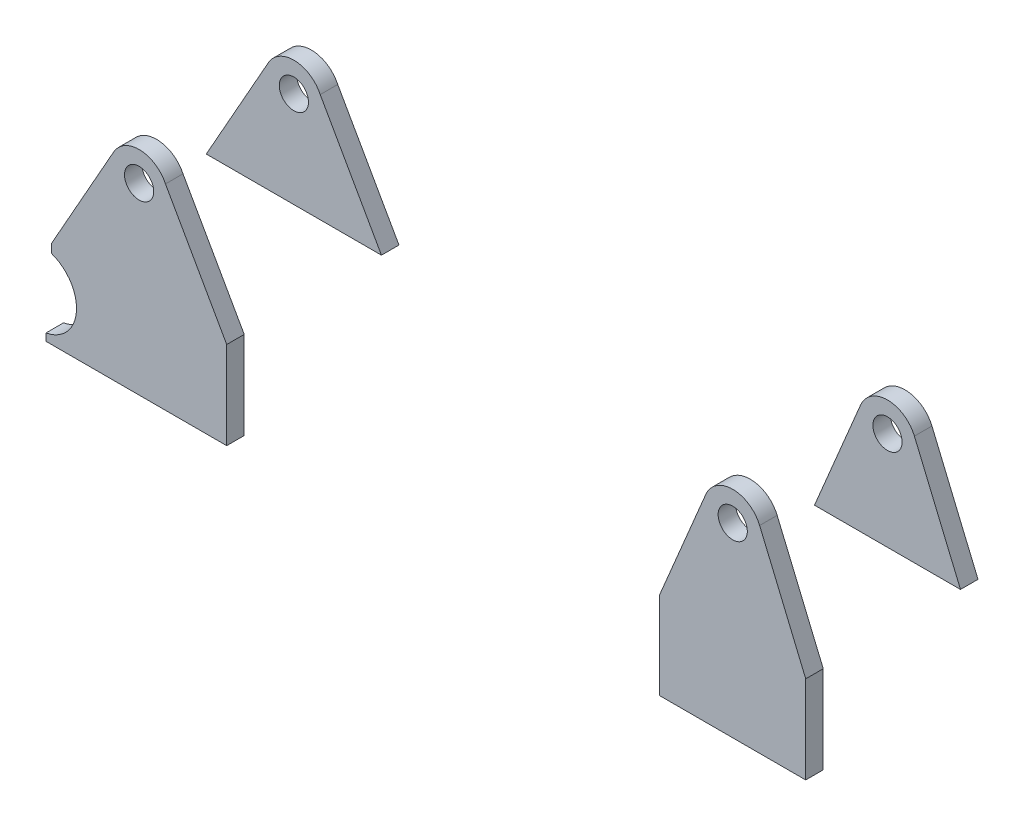
SolidWorks part; units mm, degrees
ref_plane "Front Plane" through (0, 0, 0) normal (0, 0, 1) x (1, 0, 0)
ref_plane "Top Plane" through (0, 0, 0) normal (0, 1, 0) x (1, 0, 0)
ref_plane "Right Plane" through (0, 0, 0) normal (1, 0, 0) x (0, 0, -1)
sketch "Sketch1" plane through (0, 0, 0) normal (0, 0, 1) x (1, 0, 0)
  line L0 (-745.1446, -553.3409) -> (-146.7575, -553.3409) construction
  line L1 (-745.1446, -553.3409) -> (-146.7575, -553.3409)
  line L2 (-737.4286, -553.3409) -> (-716.1399, -515.5758)
  line L3 (-698.3946, -516.1984) -> (-677.4286, -553.3409)
  line L4 (-711.9899, -518.4383) -> (-702.8674, -522.5346) construction
  line L5 (-500.2511, -516.4564) -> (-508.0021, -522.7748) construction
  line L6 (-707.4286, -520.4864) -> (-707.4286, -553.3409) construction
  line L7 (-513.3474, -515.7455) -> (-529.1266, -553.3409)
  line L9 (-494.9058, -515.7455) -> (-479.1266, -553.3409)
  line L11 (-745.1446, -583.3409) -> (-146.7582, -583.3409) construction
  line L12 (-739.3144, -583.3409) -> (-146.7582, -583.3409)
  line L16 (-677.4286, -553.3409) -> (-677.4286, -583.3409)
  line L17 (-737.4286, -553.3409) -> (-737.4286, -556.3319)
  line L19 (-504.1266, -519.6156) -> (-504.1266, -553.3409) construction
  line L20 (-529.1266, -553.3409) -> (-529.1266, -583.3409)
  line L21 (-529.1266, -583.3409) -> (-479.1266, -583.3409)
  line L22 (-479.1266, -583.3409) -> (-479.1266, -553.3409)
  line L23 (-739.3144, -580.8409) -> (-739.3144, -583.3409)
  circle A0 centre (-707.4286, -520.4864) radius 10
  circle A2 centre (-504.1266, -519.6156) radius 10
  arc A3 (-728.8602, -568.3411) -> (-754.2602, -568.3411) centre (-741.5602, -568.3411) ccw
  arc A4 (-728.8602, -568.3411) -> (-737.4286, -556.3319) centre (-741.5602, -568.3411) ccw
  arc A5 (-754.2602, -568.3411) -> (-728.8602, -568.3411) centre (-741.5602, -568.3411) ccw
  arc A6 (-739.3144, -580.8409) -> (-728.8602, -568.3411) centre (-741.5602, -568.3411) ccw
  spline S1 degree 3 poles (-702.4287, -520.5175) (-702.3667, -510.5177) (-712.3665, -510.4556) (-712.4285, -520.4554) (-712.4906, -530.4552) (-702.4908, -530.5173) (-702.4287, -520.5175) (-702.3667, -510.5177) (-712.3665, -510.4556) knots -0.5 0 0 0 0.5 0.5 0.5 1 1 1 1.5 1.5 1.5 weights 1 0.333333 0.333333 1 0.333333 0.333333 1 0.333333 0.333333 only from (-702.4287, -520.5175) to (-702.4287, -520.5175) construction
  spline S2 degree 3 poles (-499.1267, -519.6466) (-499.0647, -509.6468) (-509.0645, -509.5848) (-509.1265, -519.5846) (-509.1886, -529.5844) (-499.1887, -529.6464) (-499.1267, -519.6466) (-499.0647, -509.6468) (-509.0645, -509.5848) knots -0.5 0 0 0 0.5 0.5 0.5 1 1 1 1.5 1.5 1.5 weights 1 0.333333 0.333333 1 0.333333 0.333333 1 0.333333 0.333333 only from (-499.1267, -519.6466) to (-499.1267, -519.6466) construction
  spline S3 degree 3 poles (-702.4287, -520.5175) (-702.3667, -510.5177) (-712.3665, -510.4556) (-712.4285, -520.4554) (-712.4906, -530.4552) (-702.4908, -530.5173) (-702.4287, -520.5175) (-702.3667, -510.5177) (-712.3665, -510.4556) knots -0.5 0 0 0 0.5 0.5 0.5 1 1 1 1.5 1.5 1.5 weights 1 0.333333 0.333333 1 0.333333 0.333333 1 0.333333 0.333333 only from (-702.4287, -520.5175) to (-702.4287, -520.5175)
  spline S4 degree 3 poles (-499.1267, -519.6466) (-499.0647, -509.6468) (-509.0645, -509.5848) (-509.1265, -519.5846) (-509.1886, -529.5844) (-499.1887, -529.6464) (-499.1267, -519.6466) (-499.0647, -509.6468) (-509.0645, -509.5848) knots -0.5 0 0 0 0.5 0.5 0.5 1 1 1 1.5 1.5 1.5 weights 1 0.333333 0.333333 1 0.333333 0.333333 1 0.333333 0.333333 only from (-499.1267, -519.6466) to (-499.1267, -519.6466)
  point P4 (-707.4286, -520.4864)
  point P13 (-707.4286, -520.4864)
  point P16 (-504.1266, -519.6156)
  dimension "D1" = 20
  dimension "D2" = 30
  dimension "D4" = 20
  dimension "D3" = 30
  dimension "D5" = 25
  dimension "D6" = 25
extrude "Boss-Extrude1" add sketch "Sketch1" along normal blind 6 contours L1 L12 | L20 L1 | S4 | L1 L17 L12 L16 | A0 L2 L1 L3 | L3 A0 S3 region at (-707.4356, -541.1782, 0) region at (-705.1223, -568.3832, 0) region at (-707.0879, -510.7753, 0) region at (-504.1266, -540.8667, 0) region at (-504.1266, -568.3409, 0) region at (-504.1266, -509.8985, 0)
ref_plane "Plane1" through (0, 0, -47) normal (0, 0, -1) x (-1, 0, 0)
sketch "Sketch2" plane through (0, 0, -47) normal (0, 0, -1) x (-1, 0, 0)
  line L0 (745.1446, -553.3409) -> (146.7582, -553.3409) construction
  line L1 (745.1446, -553.3409) -> (146.7582, -553.3409)
  line L6 (737.4286, -556.3319) -> (737.4286, -553.3409)
  line L7 (737.4286, -553.3409) -> (716.1399, -515.5758)
  line L8 (698.3946, -516.1984) -> (677.4286, -553.3409)
  line L9 (677.4286, -553.3409) -> (677.4286, -583.3409)
  line L10 (677.4286, -583.3409) -> (739.3144, -583.3409)
  line L11 (739.3144, -583.3409) -> (739.3144, -580.8409)
  line L12 (737.4286, -556.3319) -> (737.4286, -553.3409)
  line L13 (737.4286, -553.3409) -> (716.1399, -515.5758)
  line L14 (698.3946, -516.1984) -> (677.4286, -553.3409)
  line L15 (677.4286, -553.3409) -> (677.4286, -583.3409)
  line L16 (677.4286, -583.3409) -> (739.3144, -583.3409)
  line L17 (739.3144, -583.3409) -> (739.3144, -580.8409)
  line L19 (479.1266, -583.3409) -> (529.1266, -583.3409)
  line L20 (529.1266, -583.3409) -> (529.1266, -553.3409)
  line L21 (529.1266, -553.3409) -> (513.3474, -515.7455)
  line L22 (494.9058, -515.7455) -> (479.1266, -553.3409)
  line L23 (479.1266, -553.3409) -> (479.1266, -583.3409)
  line L24 (479.1266, -583.3409) -> (529.1266, -583.3409)
  line L25 (529.1266, -583.3409) -> (529.1266, -553.3409)
  line L26 (529.1266, -553.3409) -> (513.3474, -515.7455)
  line L27 (494.9058, -515.7455) -> (479.1266, -553.3409)
  line L28 (479.1266, -553.3409) -> (479.1266, -583.3409)
  circle A0 centre (504.1266, -519.6156) radius 5 construction
  arc A1 (513.3474, -515.7455) -> (494.9058, -515.7455) centre (504.1266, -519.6156) ccw
  arc A2 (737.4286, -556.3319) -> (739.3144, -580.8409) centre (741.5602, -568.3411) ccw
  arc A3 (716.1399, -515.5758) -> (698.3946, -516.1984) centre (707.4286, -520.4864) ccw
  arc A4 (737.4286, -556.3319) -> (739.3144, -580.8409) centre (741.5602, -568.3411) ccw
  arc A5 (716.1399, -515.5758) -> (698.3946, -516.1984) centre (707.4286, -520.4864) ccw
  arc A6 (513.3474, -515.7455) -> (494.9058, -515.7455) centre (504.1266, -519.6156) ccw
  circle A7 centre (707.4286, -520.4864) radius 5 construction
  circle A8 centre (504.1266, -519.6156) radius 5
  circle A9 centre (707.4286, -520.4864) radius 5
  dimension "D1" = 0
  dimension "D2" = 0
extrude "Boss-Extrude2" add sketch "Sketch2" along normal blind 6 separate body contours L13 A5 L14 L1 A9 | L26 A6 L27 L1 A8 region at (-504.1266, -536.9841, -47) region at (-707.4345, -537.8062, -47)
